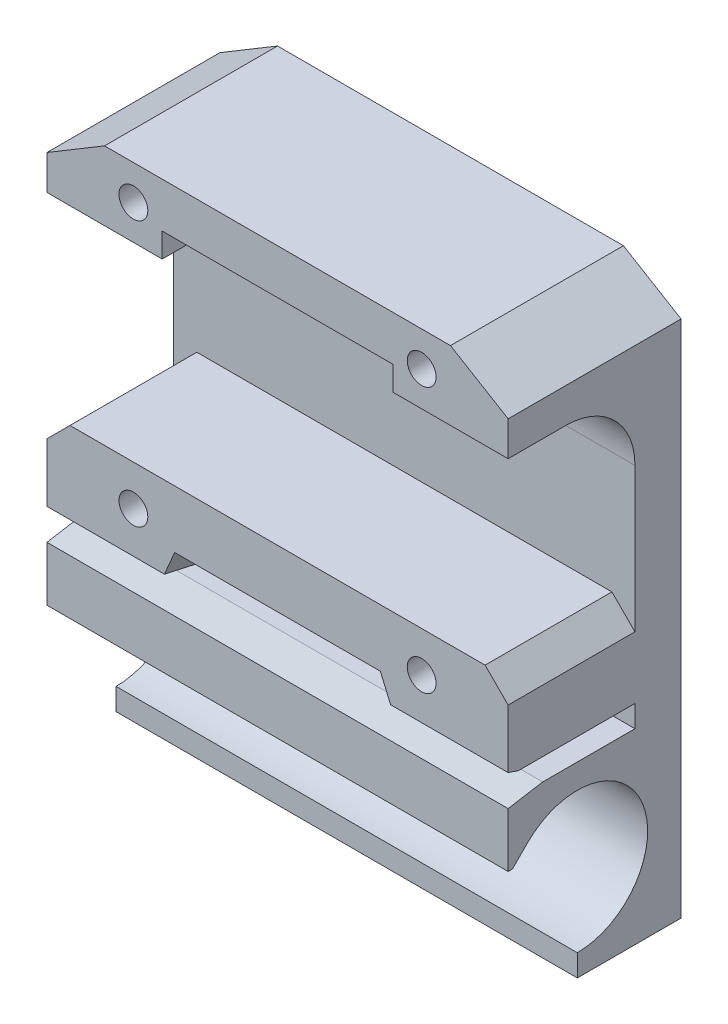
SolidWorks part; units mm, degrees
material "ABS"
ref_plane "Front Plane" through (0, 0, 0) normal (0, 0, 1) x (1, 0, 0)
ref_plane "Top Plane" through (0, 0, 0) normal (0, 1, 0) x (1, 0, 0)
ref_plane "Right Plane" through (0, 0, 0) normal (1, 0, 0) x (0, 0, -1)
sketch "Sketch1" plane through (0, 0, 0) normal (0, 0, 1) x (1, 0, 0)
  line L1 (-23.7591, 22) -> (52.715, 22) construction
  line L2 (0, -10) -> (0, 38)
  line L3 (0, 38) -> (40, 38)
  line L4 (40, -10) -> (40, 38)
  line L6 (0, -10) -> (40, -10)
  point P2 (0, 22)
  point P9 (40, 22)
  point P10 (0, 22)
  point P13 (40, 22)
  dimension "D1" = 48
  dimension "D2" = 40
extrude "Boss-Extrude1" add sketch "Sketch1" along normal blind 4
ref_plane "Plane2" through (0, 13, 0) normal (0, -1, 0) x (1, 0, 0)
sketch "Sketch2" plane through (0, 0, 4) normal (0, 0, 1) x (1, 0, 0)
  line L0 (20, 38) -> (20, 20.7808) construction
  line L1 (15.9, 33) -> (24.1, 33)
  line L2 (15.9, 33) -> (15.9, 23)
  line L3 (15.9, 23) -> (24.1, 23)
  line L4 (24.1, 33) -> (24.1, 23)
  line L5 (40, 38) -> (0, 38) construction
  line L6 (-2.2, 13) -> (2.2, 13) construction
  line L9 (2, 3) -> (10.2, 3)
  line L10 (2, 3) -> (2, -7)
  line L11 (2, -7) -> (10.2, -7)
  line L12 (10.2, 3) -> (10.2, -7)
  line L14 (29.8, 3) -> (29.8, -7)
  line L15 (38, -7) -> (29.8, -7)
  line L16 (38, 3) -> (38, -7)
  line L17 (38, 3) -> (29.8, 3)
  line L18 (15.9, 28) -> (24.1, 28) construction
  line L19 (2, -2) -> (38, -2) construction
  dimension "D1" = 8.2
  dimension "D2" = 10
  dimension "D3" = 20
  dimension "D4" = 4.1
  dimension "D5" = 30
  dimension "D6" = 2
extrude "Cut-Extrude1" [suppressed] cut sketch "Sketch2" against normal blind 1
sketch "Sketch3" [suppressed] plane through (0, 0, 3) normal (0, 0, 1) x (1, 0, 0)
  line L0 (15.9, 33) -> (15.9, 23) construction
  line L1 (15.9, 32.1) -> (24.1, 32.1)
  line L2 (15.9, 32.1) -> (15.9, 23.9)
  line L3 (15.9, 23.9) -> (24.1, 23.9)
  line L4 (24.1, 32.1) -> (24.1, 23.9)
  line L5 (24.1, 23) -> (24.1, 33) construction
  line L6 (24.1, 33) -> (15.9, 33) construction
  line L7 (15.9, 23) -> (24.1, 23) construction
  line L8 (2, 3) -> (2, -7) construction
  line L9 (2, 2.1) -> (10.2, 2.1)
  line L10 (2, 2.1) -> (2, -6.1)
  line L11 (2, -6.1) -> (10.2, -6.1)
  line L12 (10.2, 2.1) -> (10.2, -6.1)
  line L13 (10.2, -7) -> (10.2, 3) construction
  line L14 (29.8, 3) -> (29.8, -7) construction
  line L15 (29.8, 2.1) -> (38, 2.1)
  line L16 (29.8, 2.1) -> (29.8, -6.1)
  line L17 (29.8, -6.1) -> (38, -6.1)
  line L18 (38, 2.1) -> (38, -6.1)
  line L19 (38, -7) -> (38, 3) construction
  line L20 (2, -7) -> (10.2, -7) construction
  dimension "D1" = 0.9
  dimension "D2" = 0.9
  dimension "D3" = 0.9
extrude "Cut-Extrude2" [suppressed] cut sketch "Sketch3" against normal blind 4
chamfer "Chamfer1" [suppressed] distance 1 angle 45
sketch "Sketch4" [suppressed] plane through (0, 0, 3) normal (0, 0, 1) x (1, 0, 0)
  line L0 (24.1, 35.1) -> (15.9, 35.1) construction
  line L1 (15.9, 35.1) -> (15.9, 26.9) construction
  line L2 (2, 1) -> (38, 1) construction
  line L3 (2, 5.1) -> (2, -3.1) construction
  line L4 (38, -7) -> (38, 3) construction
  line L5 (6.1, 2.1) -> (6.1, -3.1) construction
  line L7 (2, -3.1) -> (10.2, -3.1) construction
  line L8 (33.9, 2.1) -> (33.9, -3.1) construction
  line L10 (29.8, -3.1) -> (38, -3.1) construction
  line L12 (10.2, 2.1) -> (2, 2.1) construction
  line L13 (38, 2.1) -> (29.8, 2.1) construction
  circle A0 centre (20, 31) radius 1.65
  circle A1 centre (6.1, 1) radius 1.65
  circle A2 centre (33.9, 1) radius 1.65
  dimension "D1" = 3.3
  dimension "D2" = 4.1
  dimension "D3" = 4.1
extrude "Cut-Extrude3" [suppressed] cut sketch "Sketch4" against normal through all
ref_plane "Plane1" through (20, 0, 0) normal (1, 0, 0) x (0, 0, -1)
sketch "Sketch5" plane through (0, 0, 4) normal (0, 0, 1) x (1, 0, 0)
  line L0 (-5.9966, 13) -> (42.103, 13) construction
  line L1 (0.9, 8.125) -> (0, 8.125)
  line L2 (40, 6.225) -> (40, 1)
  line L3 (0, 6.225) -> (40, 6.225)
  line L4 (20, 10.5) -> (20, 15.5) construction
  line L5 (40, 15.5) -> (40, 8.125)
  line L6 (20, -8.3325) -> (20, 8.3325) construction
  line L7 (0, -10) -> (40, -10) construction
  line L8 (0, 1) -> (40, 1)
  line L9 (28.9188, 10.5) -> (11.0812, 10.5)
  line L10 (31.4996, 8.125) -> (32.4683, 8.125)
  line L11 (5.9219, 8.125) -> (6.2219, 7.425)
  line L12 (11.0812, 10.5) -> (9.7634, 7.425)
  line L13 (6.2219, 7.425) -> (7.2317, 7.425)
  line L14 (-4.95, 13) -> (4.95, 13) construction
  line L15 (7.2317, 7.425) -> (7.5317, 8.125)
  line L16 (8.5004, 8.125) -> (8.8004, 7.425)
  line L17 (8.8004, 7.425) -> (9.7634, 7.425)
  line L18 (5.9219, 8.125) -> (5, 8.125)
  line L19 (35.3, 7.425) -> (36.3, 7.425)
  line L20 (35, 8.125) -> (35.3, 7.425)
  line L21 (36.6, 8.125) -> (37.5, 8.125)
  line L22 (36.3, 7.425) -> (36.6, 8.125)
  line L23 (1.2, 7.425) -> (0.9, 8.125)
  line L24 (37.8, 7.425) -> (38.8, 7.425)
  line L25 (37.5, 8.125) -> (37.8, 7.425)
  line L26 (38.8, 7.425) -> (39.1, 8.125)
  line L27 (2.5, 8.125) -> (2.2, 7.425)
  line L28 (2.2, 7.425) -> (1.2, 7.425)
  line L29 (0, -10) -> (40, -10)
  line L30 (3.7, 7.425) -> (3.4, 8.125)
  line L31 (3.4, 8.125) -> (2.5, 8.125)
  line L32 (5, 8.125) -> (4.7, 7.425)
  line L33 (4.7, 7.425) -> (3.7, 7.425)
  line L34 (0, -10) -> (0, -5)
  line L35 (34.0781, 8.125) -> (35, 8.125)
  line L36 (8.5004, 8.125) -> (7.5317, 8.125)
  line L37 (31.1996, 7.425) -> (30.2366, 7.425)
  line L38 (31.4996, 8.125) -> (31.1996, 7.425)
  line L39 (32.7683, 7.425) -> (32.4683, 8.125)
  line L40 (40, -10) -> (40, 38) construction
  line L41 (33.7781, 7.425) -> (32.7683, 7.425)
  line L42 (40, 15.5) -> (0, 15.5)
  line L43 (0, 15.5) -> (0, 8.125)
  line L44 (28.9188, 10.5) -> (30.2366, 7.425)
  line L45 (34.0781, 8.125) -> (33.7781, 7.425)
  line L46 (0, 38) -> (0, -10) construction
  line L47 (0, 32) -> (40, 32)
  line L48 (0, 32) -> (0, 38)
  line L49 (0, -5) -> (40, -5)
  line L50 (40, 32) -> (40, 38)
  line L51 (0, 38) -> (40, 38)
  line L52 (40, -10) -> (40, -5)
  line L53 (40, 38) -> (0, 38) construction
  line L54 (39.1, 8.125) -> (40, 8.125)
  line L62 (0, 6.225) -> (0, 1)
  point P84 (20, 6.225)
  dimension "D2" = 0.7
  dimension "D3" = 0.9
  dimension "D4" = 0.3
  dimension "D5" = 0.3
  dimension "D7" = 1
  dimension "D9" = 5
  dimension "D11" = 1.9
  dimension "D15" = 5
  dimension "D19" = 2.5
  dimension "D8" = 4.875
  dimension "D12" = 12
  dimension "D6" = 19
extrude "Boss-Extrude2" add sketch "Sketch5" along normal blind 11 and the other way up to surface (4 mm away) other way up to face at (20, 14, 0)
fillet "Fillet1" radius 6 2 edges at (20, 32, 4) (20, 1, 4) tangent propagation no
sketch "Sketch6" plane through (0, 0, 15) normal (0, 0, 1) x (1, 0, 0)
  line L0 (7.5, 41.1026) -> (7.5, 12.7733) construction
  line L2 (20, 38) -> (20, 13.7162) construction
  line L3 (20, -8.3325) -> (20, 8.3325) construction
  line L4 (-4.95, 13) -> (4.95, 13) construction
  line L6 (40, 38) -> (0, 38) construction
  circle A0 centre (7.5, 35) radius 1.25
  circle A1 centre (7.5, 12) radius 1.25
  circle A2 centre (32.5, 35) radius 1.25
  circle A3 centre (32.5, 12) radius 1.25
  dimension "D1" = 2.5
  dimension "D2" = 23
  dimension "D3" = 22
  dimension "D4" = 12.5
extrude "Cut-Extrude4" cut sketch "Sketch6" against normal through all
chamfer "Chamfer2" distance 2 angle 45 2 edges at (0, 15.5, 9.5) (40, 15.5, 9.5)
sketch "Sketch7" plane through (0, 0, 4) normal (0, 0, 1) x (1, 0, 0)
  line L0 (0, 26) -> (0, 13.5) construction
  line L1 (0, 22) -> (40, 22)
  line L2 (0, 22) -> (0, 15.5)
  line L3 (0, 15.5) -> (40, 15.5)
  line L4 (40, 22) -> (40, 15.5)
  line L7 (38, 15.5) -> (2, 15.5) construction
  line L8 (-4.95, 13) -> (4.95, 13) construction
  dimension "D1" = 9
extrude "Cut-Extrude5" [suppressed] cut sketch "Sketch7" against normal blind 3
fillet "Fillet2" [suppressed] radius 3
chamfer "Chamfer3" distance 3 distance2 1 3 edges at (1.7, 7.425, 15) (4.2, 7.425, 15) (30.7181, 7.425, 15) first distance on face at (1.7, 7.425, 9.5) first distance on face at (4.2, 7.425, 9.5) first distance on face at (30.7181, 7.425, 9.5)
chamfer "Chamfer4" distance 3 distance2 0.5 1 edges at (20, 6.225, 15) first distance on face at (20, 6.225, 9.5)
sketch "Sketch8" plane through (20, 0, 0) normal (1, 0, 0) x (0, 0, -1)
  line L0 (-9, 28) -> (-9, -2) construction
  line L1 (-15, 38) -> (0, 38) construction
  line L2 (-4, 6.225) -> (-4, 8.125) construction
  line L4 (-9, 34.1) -> (-18.8209, 34.1)
  line L5 (-18.8209, 34.1) -> (-18.8209, 21.9)
  line L6 (-18.8209, 21.9) -> (-9, 21.9)
  arc A0 (-9, 21.9) -> (-9, 34.1) centre (-9, 28) ccw
  dimension "D1" = 30
  dimension "D3" = 10
  dimension "D4" = 5
extrude "Cut-Extrude6" cut sketch "Sketch8" against normal blind 10 and the other way blind 10
sketch "Sketch12" plane through (0, 38, 0) normal (0, 1, 0) x (1, 0, 0)
  line L1 (10, -4) -> (0, -4) construction
  circle A0 centre (15.4, -9) radius 3
  dimension "D3" = 6
  dimension "D1" = 5
  dimension "D2" = 15.4
extrude "Cut-Extrude8" [suppressed] cut sketch "Sketch12" against normal up to surface (22.5 mm away) up to face at (20, 15.5, 9.5)
sketch "Sketch13" [suppressed] plane through (0, 15.5, 0) normal (0, 1, 0) x (1, 0, 0)
  circle A0 centre (15.4, -9) radius 1.5
  circle A1 centre (15.4, -9) radius 3 construction
  dimension "D1" = 3
extrude "Cut-Extrude10" [suppressed] cut sketch "Sketch13" against normal offset from surface (10.275 mm away) 1 up to face at (20, 6.225, 8) offset beyond the face yes
sketch "Sketch9" [suppressed] plane through (0, 13, 0) normal (0, -1, 0) x (1, 0, 0)
  line L0 (12.5, 16.8153) -> (18.3, 16.8153)
  line L1 (15.4, 5.6514) -> (18.3, 7.3257)
  line L2 (18.3, 7.3257) -> (18.3, 16.8153)
  line L5 (12.5, 16.8153) -> (12.5, 7.3257)
  line L6 (12.5, 7.3257) -> (15.4, 5.6514)
  line L8 (13.9872, 11.5329) -> (12.1308, 10.4612) [skipped]
  line L9 (16.8128, 11.5329) -> (14.9564, 12.6047) [skipped]
  circle A0 centre (15.4, 9) radius 2.9 construction
  arc A1 (18.4, 9) -> (12.4, 9) centre (15.4, 9) ccw construction
  dimension "D1" = 5.8
extrude "Cut-Extrude7" [suppressed] cut sketch "Sketch9" against normal blind 1.25 and the other way blind 1.25
chamfer "Chamfer5" distance 5 distance2 3 1 edges at (0, 38, 7.5) first distance on face at (20, 38, 7.5)
chamfer "Chamfer6" distance 3 distance2 5 1 edges at (40, 38, 7.5) first distance on face at (40, 11.0703, 9.6639)
sketch "Sketch14" plane through (0, 0, 0) normal (0, 0, -1) x (-1, 0, 0)
  line L1 (0, 35) -> (0, -10) construction
  line L4 (-18, 28.5) -> (-5, 28.5) construction
  line L6 (-35, 38) -> (-5, 38) construction
  circle A4 centre (-5, 28.5) radius 1.35
  circle A5 centre (-18, 28.5) radius 1.35
  dimension "D11" = 5
  dimension "D14" = 2.7
  dimension "D10" = 9.5
  dimension "D12" = 13
extrude "Cut-Extrude11" [suppressed] cut sketch "Sketch14" against normal blind 10
sketch "Sketch15" plane through (20, 0, 0) normal (1, 0, 0) x (0, 0, -1)
  line L0 (-9, 28) -> (-9, -2) construction
  line L1 (-15, 38) -> (0, 38) construction
  line L2 (-4, 13.5) -> (-4, 26) construction
  circle A0 centre (-9, -2) radius 3.5
  circle A1 centre (-9, 28) radius 3.5 construction
  dimension "D1" = 7
  dimension "D3" = 10
  dimension "D2" = 30
  dimension "D4" = 5
extrude "Cut-Extrude12" cut sketch "Sketch15" against normal through all and the other way through all
sketch "Sketch16" plane through (20, 0, -20) normal (-1, 0, 0) x (0, 0, 1)
  line L0 (29, 28) -> (29, -2) construction
  line L1 (29, -10.4726) -> (38.8209, -10.4726)
  line L2 (29, -8.1) -> (29, -10.4726)
  line L3 (38.8209, -3.1942) -> (33.3134, 2.3134)
  line L7 (38.8209, -10.4726) -> (38.8209, -3.1942)
  arc A1 (29, 34.1) -> (24, 24.5057) centre (29, 28) ccw construction
  arc A2 (29, -8.1) -> (33.3134, 2.3134) centre (29, -2) cw
  dimension "D1" = 30
extrude "Cut-Extrude13" cut sketch "Sketch16" against normal through all and the other way through all
